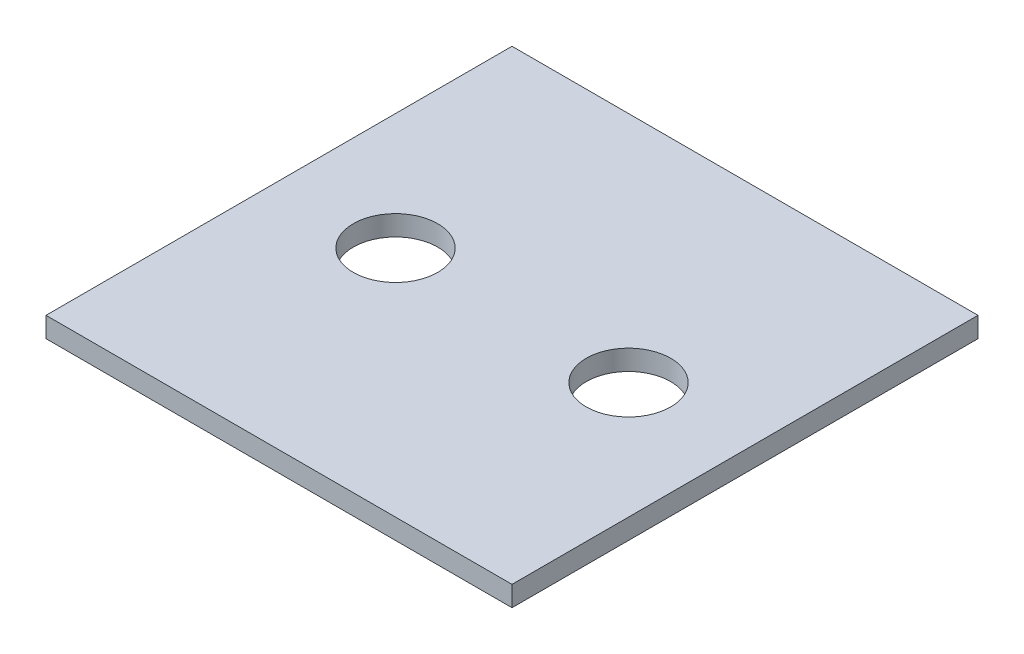
SolidWorks part; units mm, degrees
material "Pine"
ref_plane "Front Plane" through (0, 0, 0) normal (0, 0, 1) x (1, 0, 0)
ref_plane "Top Plane" through (0, 0, 0) normal (0, 1, 0) x (1, 0, 0)
ref_plane "Right Plane" through (0, 0, 0) normal (1, 0, 0) x (0, 0, -1)
sketch "Sketch1" plane through (0, 0, 0) normal (0, 1, 0) x (1, 0, 0)
  line L0 (69, 276) -> (69, 0) construction
  line L1 (0, 0) -> (276, 0)
  line L2 (0, 0) -> (0, 276)
  line L3 (0, 276) -> (276, 276)
  line L4 (276, 0) -> (276, 276)
  line L5 (0, 138) -> (276, 138) construction
  line L6 (207, 276) -> (207, 0) construction
  circle A0 centre (69, 138) radius 25
  circle A1 centre (207, 138) radius 25
  dimension "D5" = 50
  dimension "D6" = 50
  dimension "D1" = 276
  dimension "D2" = 276
  dimension "D3" = 69
  dimension "D4" = 69
extrude "Boss-Extrude1" add sketch "Sketch1" along normal blind 12
equation "\"D3@Sketch1\"=276/4"
equation "\"D4@Sketch1\"=276/4"
